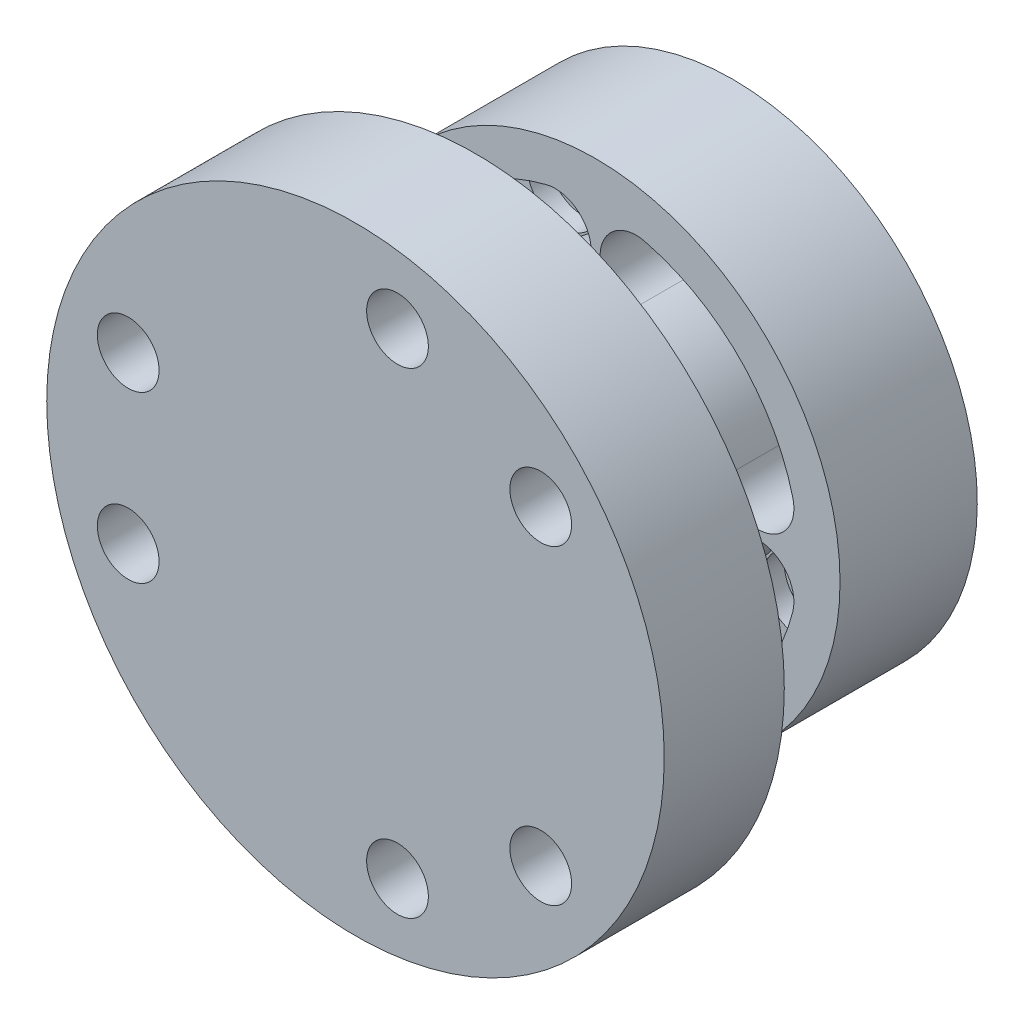
SolidWorks part; units mm, degrees
ref_plane "정면" through (0, 0, 0) normal (0, 0, 1) x (1, 0, 0)
ref_plane "윗면" through (0, 0, 0) normal (0, 1, 0) x (1, 0, 0)
ref_plane "우측면" through (0, 0, 0) normal (1, 0, 0) x (0, 0, -1)
sketch "스케치1" plane through (0, 0, 0) normal (0, 0, 1) x (1, 0, 0)
  line L0 (0, 0) -> (6.8943, 6.8943) construction
  line L1 (0, 0) -> (9.75, 0) construction
  line L2 (-4.25, -5.5621) -> (-4.25, -13.6015)
  line L3 (0, 0) -> (0, -14.25) construction
  line L4 (4.25, -5.5621) -> (4.25, -13.6015)
  arc A0 (4.25, -13.6015) -> (-4.25, -13.6015) centre (0, 0) ccw
  circle A1 centre (6.8943, 6.8943) radius 1.1
  circle A2 centre (0, 9.75) radius 2.1 construction
  circle A3 centre (0, 0) radius 9.75 construction
  arc A4 (4.25, -5.5621) -> (-4.25, -5.5621) centre (0, 0) ccw
  circle A5 centre (6.8943, -6.8943) radius 1.1
  circle A6 centre (-6.8943, -6.8943) radius 1.1
  circle A7 centre (-6.8943, 6.8943) radius 1.1
  point P19 (0, 0)
  dimension "D1" = 28.5
  dimension "D2" = 4.2
  dimension "D6" = 2.2
  dimension "D7" = 4.25
  dimension "D3" = 19.5
  dimension "D4" = 14
  dimension "D5" = 45
extrude "보스-돌출1" add sketch "스케치1" along normal blind 3
sketch "스케치2" plane through (0, 0, 3) normal (0, 0, 1) x (1, 0, 0)
  circle A0 centre (-6.8943, 6.8943) radius 2.1
  circle A1 centre (6.8943, 6.8943) radius 2.1
  circle A2 centre (6.8943, -6.8943) radius 2.1
  circle A3 centre (-6.8943, -6.8943) radius 2.1
  point P11 (0, 0)
  dimension "D2" = 4.2
  dimension "D1" = 4
extrude "컷-돌출1" cut sketch "스케치2" against normal blind 1.2
sketch "스케치3" plane through (0, 0, 3) normal (0, 0, 1) x (1, 0, 0)
  circle A0 centre (0, 0) radius 14.25
  circle A1 centre (0, 0) radius 11.85
  dimension "D1" = 28.5
  dimension "D2" = 23.7
extrude "보스-돌출2" add sketch "스케치3" along normal blind 1
sketch "스케치4" plane through (0, 0, 4) normal (0, 0, 1) x (1, 0, 0)
  line L0 (0, 0) -> (0, 14.25) construction
  line L1 (0, 0) -> (10.0763, 10.0763) construction
  line L2 (0, 0) -> (2.3587, 9.4604) construction
  line L3 (2.6995, 5.0769) -> (0, 0) construction
  circle A0 centre (0, 0) radius 14.25
  arc A1 (2.3587, 9.4604) -> (9.4604, 2.3587) centre (0, 0) cw construction
  arc A2 (11.498, 2.8668) -> (2.8668, 11.498) centre (0, 0) ccw
  arc A3 (7.4228, 1.8507) -> (1.8507, 7.4228) centre (0, 0) ccw
  arc A4 (7.4228, 1.8507) -> (11.498, 2.8668) centre (9.4604, 2.3587) ccw
  arc A5 (2.8668, 11.498) -> (1.8507, 7.4228) centre (2.3587, 9.4604) ccw
  arc A6 (8.3792, -8.3792) -> (8.3792, 8.3792) centre (0, 0) ccw construction
  arc A7 (-2.6995, 5.0769) -> (2.6995, 5.0769) centre (0, 0) cw construction
  circle A8 centre (0, 0) radius 11.85 construction
  circle A9 centre (0, 0) radius 3.25 construction
  circle A10 centre (0, 0) radius 4 construction
  circle A11 centre (6.8943, 6.8943) radius 2.1 construction
  arc A12 (9.4604, -2.3587) -> (2.3587, -9.4604) centre (0, 0) cw construction
  arc A13 (2.8668, -11.498) -> (11.498, -2.8668) centre (0, 0) ccw
  arc A14 (1.8507, -7.4228) -> (7.4228, -1.8507) centre (0, 0) ccw
  arc A15 (1.8507, -7.4228) -> (2.8668, -11.498) centre (2.3587, -9.4604) ccw
  arc A16 (11.498, -2.8668) -> (7.4228, -1.8507) centre (9.4604, -2.3587) ccw
  arc A17 (-2.3587, -9.4604) -> (-9.4604, -2.3587) centre (0, 0) cw construction
  arc A18 (-11.498, -2.8668) -> (-2.8668, -11.498) centre (0, 0) ccw
  arc A19 (-7.4228, -1.8507) -> (-1.8507, -7.4228) centre (0, 0) ccw
  arc A20 (-7.4228, -1.8507) -> (-11.498, -2.8668) centre (-9.4604, -2.3587) ccw
  arc A21 (-2.8668, -11.498) -> (-1.8507, -7.4228) centre (-2.3587, -9.4604) ccw
  arc A22 (-9.4604, 2.3587) -> (-2.3587, 9.4604) centre (0, 0) cw construction
  arc A23 (-2.8668, 11.498) -> (-11.498, 2.8668) centre (0, 0) ccw
  arc A24 (-1.8507, 7.4228) -> (-7.4228, 1.8507) centre (0, 0) ccw
  arc A25 (-1.8507, 7.4228) -> (-2.8668, 11.498) centre (-2.3587, 9.4604) ccw
  arc A26 (-11.498, 2.8668) -> (-7.4228, 1.8507) centre (-9.4604, 2.3587) ccw
  arc A27 (3.4037, 6.4014) -> (-3.4037, 6.4014) centre (0, 0) ccw
  arc A28 (1.9953, 3.7525) -> (-1.9953, 3.7525) centre (0, 0) ccw
  arc A29 (1.9953, 3.7525) -> (3.4037, 6.4014) centre (2.6995, 5.0769) ccw
  arc A30 (-3.4037, 6.4014) -> (-1.9953, 3.7525) centre (-2.6995, 5.0769) ccw
  arc A31 (5.0769, 2.6995) -> (5.0769, -2.6995) centre (0, 0) cw construction
  arc A32 (6.4014, -3.4037) -> (6.4014, 3.4037) centre (0, 0) ccw
  arc A33 (3.7525, -1.9953) -> (3.7525, 1.9953) centre (0, 0) ccw
  arc A34 (3.7525, -1.9953) -> (6.4014, -3.4037) centre (5.0769, -2.6995) ccw
  arc A35 (6.4014, 3.4037) -> (3.7525, 1.9953) centre (5.0769, 2.6995) ccw
  arc A36 (2.6995, -5.0769) -> (-2.6995, -5.0769) centre (0, 0) cw construction
  arc A37 (-3.4037, -6.4014) -> (3.4037, -6.4014) centre (0, 0) ccw
  arc A38 (-1.9953, -3.7525) -> (1.9953, -3.7525) centre (0, 0) ccw
  arc A39 (-1.9953, -3.7525) -> (-3.4037, -6.4014) centre (-2.6995, -5.0769) ccw
  arc A40 (3.4037, -6.4014) -> (1.9953, -3.7525) centre (2.6995, -5.0769) ccw
  arc A41 (-5.0769, -2.6995) -> (-5.0769, 2.6995) centre (0, 0) cw construction
  arc A42 (-6.4014, 3.4037) -> (-6.4014, -3.4037) centre (0, 0) ccw
  arc A43 (-3.7525, 1.9953) -> (-3.7525, -1.9953) centre (0, 0) ccw
  arc A44 (-3.7525, 1.9953) -> (-6.4014, 3.4037) centre (-5.0769, 2.6995) ccw
  arc A45 (-6.4014, -3.4037) -> (-3.7525, -1.9953) centre (-5.0769, -2.6995) ccw
  point P6 (6.8943, 6.8943)
  point P28 (6.8943, -6.8943)
  point P35 (-6.8943, -6.8943)
  point P42 (-6.8943, 6.8943)
  point P47 (0, 0)
  point P48 (0, 5.75)
  point P59 (5.75, 0)
  point P66 (0, -5.75)
  point P73 (-5.75, 0)
  point P78 (0, 0)
  dimension "D2" = 28.5
  dimension "D3" = 6.5
  dimension "D4" = 8
  dimension "D5" = 31
  dimension "D7" = 7.65
  dimension "D8" = 7.25
  dimension "D9" = 4.25
  dimension "D1" = 45
  dimension "D10" = 28
  dimension "D6" = 4
extrude "보스-돌출3" add sketch "스케치4" along normal blind 4
sketch "스케치5" plane through (0, 0, 4) normal (0, 0, -1) x (-1, 0, 0)
  circle A0 centre (0, 0) radius 3.25
  dimension "D1" = 6.5
extrude "컷-돌출2" cut sketch "스케치5" against normal blind 2.5
sketch "스케치6" plane through (0, 0, 8) normal (0, 0, 1) x (1, 0, 0)
  circle A0 centre (0, 0) radius 3.5
  dimension "D1" = 7
extrude "보스-돌출4" add sketch "스케치6" along normal blind 7
sketch "스케치7" plane through (0, 0, 15) normal (0, 0, 1) x (1, 0, 0)
  line L0 (0, 0) -> (-14.1, 0) construction
  line L1 (0, 0) -> (-13.2497, 4.8225) construction
  circle A0 centre (0, 0) radius 14.1 construction
  circle A1 centre (-13.2497, 4.8225) radius 1.6
  circle A2 centre (0, 0) radius 18
  circle A3 centre (-13.2497, -4.8225) radius 1.6
  circle A4 centre (10.8012, 9.0633) radius 1.6
  circle A5 centre (2.4484, 13.8858) radius 1.6
  circle A6 centre (2.4484, -13.8858) radius 1.6
  circle A7 centre (10.8012, -9.0633) radius 1.6
  point P20 (0, 0)
  dimension "D1" = 28.2
  dimension "D3" = 3.2
  dimension "D4" = 36
  dimension "D2" = 20
extrude "보스-돌출5" add sketch "스케치7" along normal blind 7
sketch "스케치8" plane through (0, 0, 15) normal (0, 0, -1) x (-1, 0, 0)
  circle A0 centre (13.2497, 4.8225) radius 2.75
  circle A1 centre (13.2497, -4.8225) radius 2.75
  circle A2 centre (-2.4484, -13.8858) radius 2.75
  circle A3 centre (-10.8012, -9.0633) radius 2.75
  circle A4 centre (-10.8012, 9.0633) radius 2.75
  circle A5 centre (-2.4484, 13.8858) radius 2.75
  point P17 (0, 0)
  dimension "D1" = 5.5
  dimension "D2" = 5.5
hole_wizard "M3 접시 머리 나사용 카운터싱크1" positions "3D스케치1" profile "스케치9" countersink size "M3" standard "ISO" end condition through all
sketch3d "3D스케치1"
  point P0 (2.4484, 13.8858, 15)
  point P3 (-13.2497, 4.8225, 15)
  point P6 (-13.2497, -4.8225, 15)
  point P9 (2.4484, -13.8858, 15)
  point P12 (10.8012, -9.0633, 15)
  point P15 (10.8012, 9.0633, 15)
sketch "스케치9" plane through (2.4484, 13.8858, 15) normal (1, 0, 0) x (0, 1, 0)
  line L0 (0, 0) -> (0, 7)
  line L1 (0, 7) -> (1.8, 7)
  line L2 (1.8, 7) -> (1.8, 1.35)
  line L3 (1.8, 1.35) -> (3.15, 0)
  line L5 (3.15, 0) -> (0, 0)
  line L6 (-1.8, 1.35) -> (-3.15, 0) construction
  line L11 (0, -6.35) -> (0, 107.95) construction
  dimension "관통 구멍 지름" = 3.6
  dimension "관통 구멍 깊이" = 7
  dimension "표면 카운터싱크 지름" = 6.3
  dimension "표면 카운터싱크 각도" = 90
ref_axis "기준축1" through (0, 0, 22) along (0, 0, -1)
